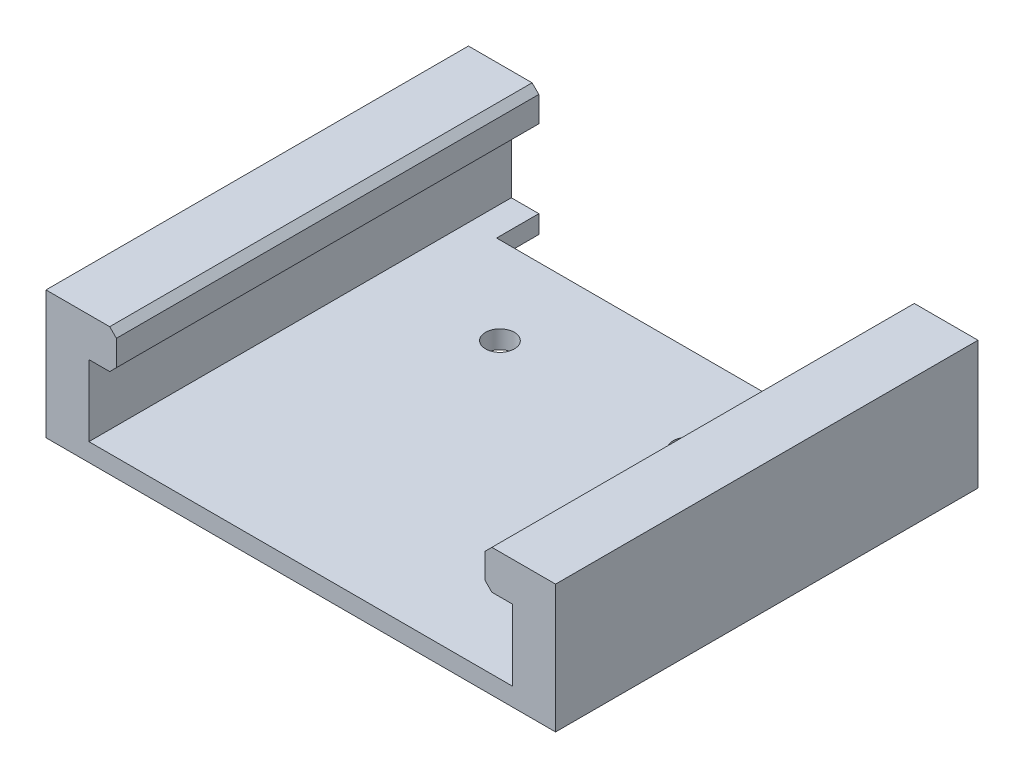
SolidWorks part; units mm, degrees
material "1060 合金"
ref_plane "前视基准面" through (0, 0, 0) normal (0, 0, 1) x (1, 0, 0)
ref_plane "上视基准面" through (0, 0, 0) normal (0, 1, 0) x (1, 0, 0)
ref_plane "右视基准面" through (0, 0, 0) normal (1, 0, 0) x (0, 0, -1)
sketch "草图1" plane through (0, 0, 0) normal (0, 0, 1) x (1, 0, 0)
  line L0 (-27.5, 19.1) -> (-38, 19.1)
  line L1 (-38, 19.1) -> (-38, 0)
  line L2 (-27.5, 19.1) -> (-27.5, 13.3)
  line L3 (-27.5, 13.3) -> (-31.6, 13.3)
  line L4 (-31.6, 13.3) -> (-31.6, 2.7)
  line L5 (0, 0) -> (0, 43.3652) construction
  line L6 (31.6, 13.3) -> (31.6, 2.7)
  line L7 (27.5, 13.3) -> (31.6, 13.3)
  line L8 (27.5, 19.1) -> (27.5, 13.3)
  line L9 (38, 19.1) -> (38, 0)
  line L10 (27.5, 19.1) -> (38, 19.1)
  line L11 (-31.6, 2.7) -> (31.6, 2.7)
  line L12 (-38, 0) -> (38, 0)
  dimension "D1" = 63.2
  dimension "D2" = 55
  dimension "D3" = 5.8
  dimension "D4" = 10.6
  dimension "D5" = 76
  dimension "D6" = 19.1
extrude "凸台-拉伸1" add sketch "草图1" along normal mid plane 63
hole_wizard "M3 螺纹孔1" positions "草图3" profile "草图2" tap size "M3" standard "GB"
sketch "草图3" plane through (0, 0, 0) normal (0, -1, 0) x (-1, 0, 0)
  line L0 (0, 0) -> (0, 40.318) construction
  line L2 (38, -31.5) -> (-38, -31.5) construction
  line L3 (38, 31.5) -> (-38, 31.5) construction
  point P0 (34.8, 25.5)
  point P2 (34.8, -25.5)
  point P12 (-34.8, -25.5)
  point P13 (-34.8, 25.5)
  dimension "D1" = 69.6
  dimension "D2" = 6
  dimension "D3" = 6
sketch "草图2" plane through (-34.8, 0, -25.5) normal (1, 0, 0) x (0, 0, -1)
  line L0 (0, 0) -> (0, 14.7511)
  line L1 (0, 14.7511) -> (1.25, 14)
  line L2 (1.25, 14) -> (1.25, 13.5)
  line L3 (1.25, 13.5) -> (1.5, 13.5)
  line L4 (1.5, 13.5) -> (1.5, 0)
  line L5 (1.5, 0) -> (0, 0)
  line L10 (0, 14.7511) -> (-1.25, 14) construction
  line L11 (0, -6.35) -> (0, 107.95) construction
  dimension "螺纹孔钻头直径" = 2.5
  dimension "螺纹孔钻头深度" = 14
  dimension "螺纹主直径" = 3
  dimension "螺纹深度" = 13.5
  dimension "导头角度" = 118
hole_wizard "M4 间隙孔1" positions "草图5" profile "草图4" hole size "M4" standard "GB" end condition up to next
sketch "草图5" plane through (0, 0, 0) normal (0, -1, 0) x (-1, 0, 0)
  line L1 (0, 0) -> (0, 26.3665) construction
  line L3 (38, 31.5) -> (-38, 31.5) construction
  point P0 (-14, 12.2)
  point P2 (14, 12.2)
  dimension "D1" = 28
  dimension "D2" = 19.3
sketch "草图4" plane through (14, 0, -12.2) normal (1, 0, 0) x (0, 0, -1)
  line L0 (0, 0) -> (0, 2.7)
  line L1 (0, 2.7) -> (2.15, 2.7)
  line L2 (2.15, 2.7) -> (2.15, 0)
  line L5 (2.15, 0) -> (0, 0)
  line L11 (0, -6.35) -> (0, 107.95) construction
  dimension "通孔孔直径" = 4.3
  dimension "通孔孔深度" = 2.7
sketch "草图6" plane through (0, 2.7, 0) normal (0, 1, 0) x (1, 0, 0)
  line L1 (-27.5, 31.5) -> (27.5, 31.5)
  line L2 (-27.5, 31.5) -> (-27.5, 25.2)
  line L3 (-27.5, 25.2) -> (27.5, 25.2)
  line L4 (27.5, 31.5) -> (27.5, 25.2)
  line L5 (-27.5, 31.5) -> (27.5, 25.2) construction
  line L6 (-27.5, 25.2) -> (27.5, 31.5) construction
  line L7 (27.5, -31.5) -> (27.5, 31.5) construction
  line L8 (31.6, 31.5) -> (-31.6, 31.5) construction
  point P0 (0, 28.35)
  dimension "D1" = 0
  dimension "D2" = 6.3
extrude "切除-拉伸1" cut sketch "草图6" against normal up to next
chamfer "倒角1" distance 1 angle 45 4 edges at (27.5, 13.3, 0) (27.5, 19.1, 0) (-27.5, 19.1, 0) (-27.5, 13.3, 0)
